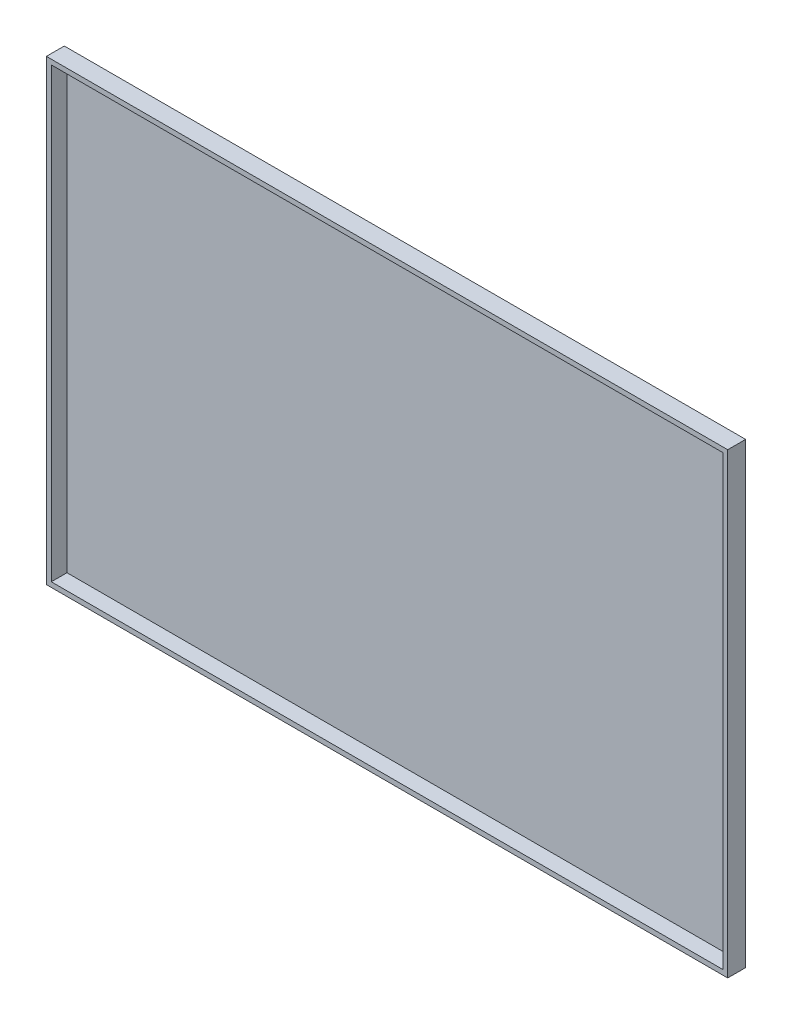
SolidWorks part; units mm, degrees
ref_plane "Front Plane" through (0, 0, 0) normal (0, 0, 1) x (1, 0, 0)
ref_plane "Top Plane" through (0, 0, 0) normal (0, 1, 0) x (1, 0, 0)
ref_plane "Right Plane" through (0, 0, 0) normal (1, 0, 0) x (0, 0, -1)
sketch "Sketch1" plane through (0, 0, 0) normal (0, 0, 1) x (1, 0, 0)
  line L1 (-1500, 1000) -> (1500, 1000)
  line L2 (-1500, 1000) -> (-1500, -1000)
  line L3 (-1500, -1000) -> (1500, -1000)
  line L4 (1500, 1000) -> (1500, -1000)
  line L5 (-1500, 1000) -> (1500, -1000) construction
  line L6 (-1500, -1000) -> (1500, 1000) construction
  line L7 (-1522, 1022) -> (1522, 1022)
  line L8 (-1522, 1022) -> (-1522, -1022)
  line L9 (-1522, -1022) -> (1522, -1022)
  line L10 (1522, 1022) -> (1522, -1022)
  line L11 (-1522, 1022) -> (1522, -1022) construction
  line L12 (-1522, -1022) -> (1522, 1022) construction
  point P0 (0, 0)
  point P5 (0, 0)
  dimension "D1" = 2000
  dimension "D2" = 3000
  dimension "D3" = 22
  dimension "D4" = 22
extrude "Boss-Extrude1" add sketch "Sketch1" along normal blind 10 contours L4 L1 L2 L3 | L10 L7 L8 L9 L1 L4 L3 L2 region at (0, 0, 0) region at (0, 1018.3334, 0)
extrude "Boss-Extrude2" add sketch "Sketch1<3>" along normal blind 80
sketch "Sketch1<3>" plane through (0, 0, 0) normal (0, 0, 1) x (1, 0, 0) same geometry as "Sketch1"
sketch "Sketch3" plane through (0, 0, 10) normal (0, 0, 1) x (1, 0, 0)
  line L0 (300.7126, 417.7727) -> (1153.3793, 417.7727) construction
